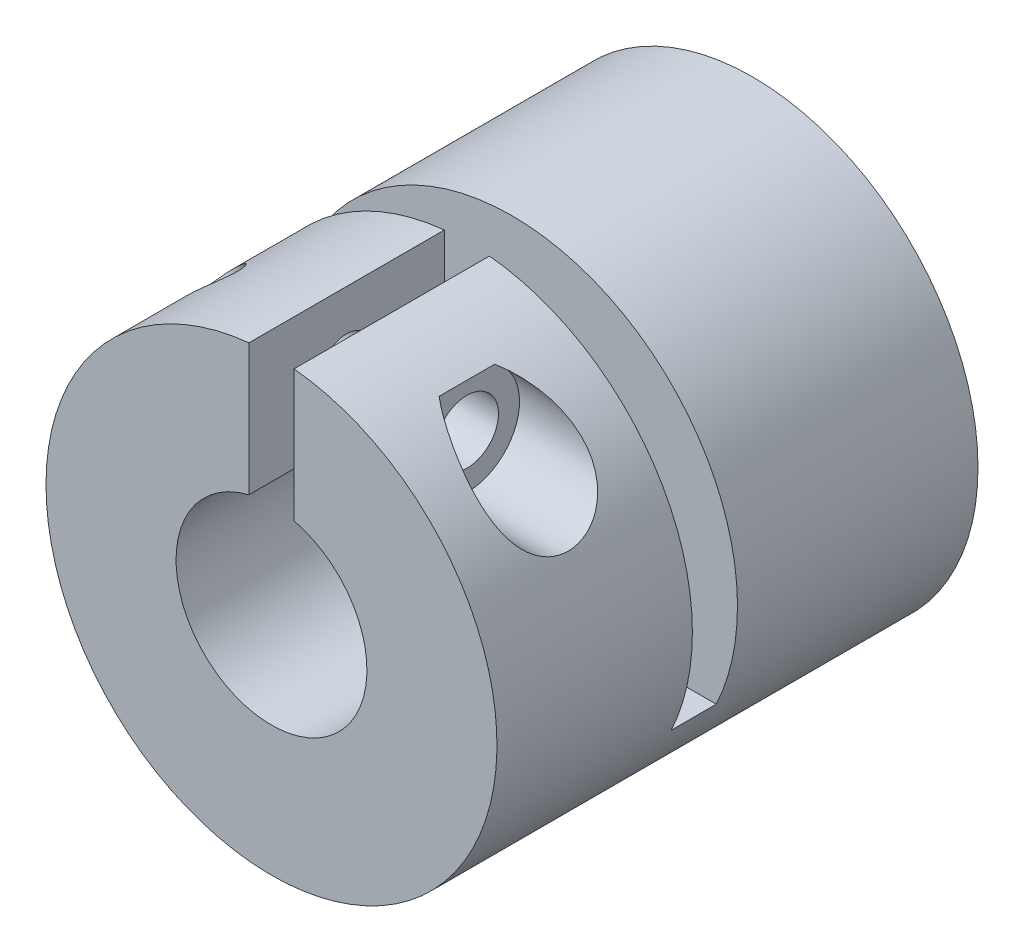
SolidWorks part; units mm, degrees
note: '?' marks a value the reader was unsure of.
ref_plane "Front Plane" through (0, 0, 0) normal (0, 0, 1) x (1, 0, 0)
ref_plane "Top Plane" through (0, 0, 0) normal (0, 1, 0) x (1, 0, 0)
ref_plane "Right Plane" through (0, 0, 0) normal (1, 0, 0) x (0, 0, -1)
sketch "Sketch1" plane through (0, 0, 0) normal (0, 0, 1) x (1, 0, 0)
  circle A0 centre (0, 0) radius 15
  circle A1 centre (0, 0) radius 6.35
  dimension "D1" = 30
  dimension "D2" = 12.7
extrude "Boss-Extrude1" add sketch "Sketch1" along normal blind 32
sketch "Sketch2" plane through (0, 0, 32) normal (0, 0, 1) x (1, 0, 0)
  line L0 (0, 0) -> (0, 15) construction
  line L1 (0, 6.1703) -> (0, 14.9248) construction
  line L2 (-1.5, 6.1703) -> (-1.5, 14.9248)
  line L3 (1.5, 6.1703) -> (1.5, 14.9248)
  circle A0 centre (0, 0) radius 15 construction
  arc A1 (-1.5, 6.1703) -> (1.5, 6.1703) centre (0, 6.1703) ccw
  arc A2 (1.5, 14.9248) -> (-1.5, 14.9248) centre (0, 14.9248) ccw
  circle A3 centre (0, 0) radius 6.35 construction
  point P9 (0, 10.5476)
  dimension "D1" = 3
extrude "Cut-Extrude1" cut sketch "Sketch2" against normal blind 16
ref_axis "Axis1" through (0, 0, 32) along (0, 0, -1)?
ref_plane "Plane1" through (0, 15, 0) normal (0, 1, 0) x (1, 0, 0)
sketch "Sketch3" plane through (0, 15, 0) normal (0, 1, 0) x (1, 0, 0)
  line L0 (0, -16) -> (15, -16) construction
  line L1 (0, -32) -> (0, 0) construction
  line L2 (15, -32) -> (15, 0) construction
  line L3 (-1.5, -16) -> (1.5, -16) construction
  line L4 (-15, -16) -> (15, -16)
  line L5 (15, -16) -> (15, -19)
  line L6 (15, -19) -> (-15, -19)
  line L7 (0, -16) -> (0, -19) construction
  line L8 (-15, -16) -> (-15, -19)
extrude "Cut-Extrude2" cut sketch "Sketch3" against normal up to vertex (30.001 mm away)
sketch "Sketch4" plane through (-1.5, 0, 0) normal (1, 0, 0) x (0, 0, -1)
  line L0 (-25.5, 14.9248) -> (-25.5, 6.1703) construction
  line L1 (-19, 14.9248) -> (-32, 14.9248) construction
  line L2 (-19, 6.1703) -> (-32, 6.1703) construction
  circle A0 centre (-25.5, 10.5476) radius 1.65
  dimension "D1" = 3.3
extrude "Cut-Extrude3" cut sketch "Sketch4" against normal through all and the other way through all
sketch "Sketch5" plane through (1.5, 0, 0) normal (-1, 0, 0) x (0, 0, 1)
  circle A0 centre (25.5, 10.5476) radius 2.1
  dimension "D1" = 4.2
extrude "Cut-Extrude4" cut sketch "Sketch5" against normal through all
ref_plane "Plane2" through (15, 0, 0) normal (1, 0, 0) x (0, 0, -1)
sketch "Sketch6" plane through (15, 0, 0) normal (1, 0, 0) x (0, 0, -1)
  circle A0 centre (-25.5, 10.5476) radius 3.5
  circle A1 centre (-25.5, 10.5476) radius 2.1 construction
  dimension "D1" = 7
extrude "Cut-Extrude5" cut sketch "Sketch6" against normal offset from surface (8.5 mm away) 5 up to face at (1.5, 10.5476, 27.6)
